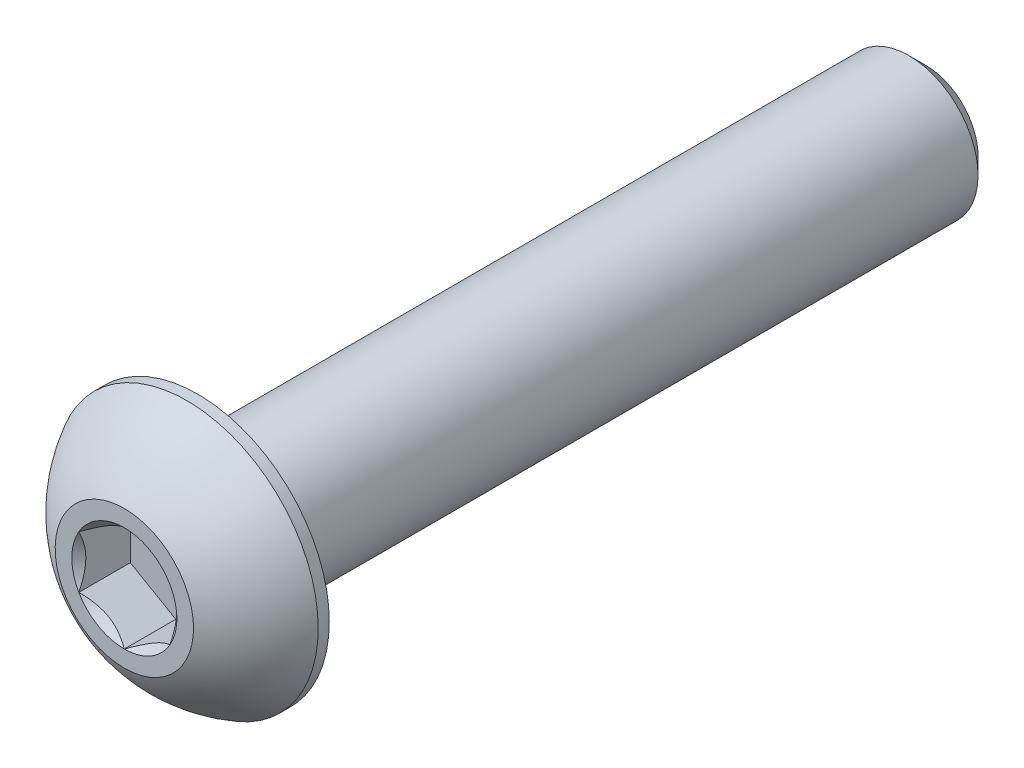
SolidWorks part; units mm, degrees
ref_plane "Front" through (0, 0, 0) normal (0, 0, 1) x (1, 0, 0)
ref_plane "Top" through (0, 0, 0) normal (0, 1, 0) x (1, 0, 0)
ref_plane "Right" through (0, 0, 0) normal (1, 0, 0) x (0, 0, -1)
sketch "Sketch1" plane through (0, 0, 0) normal (1, 0, 0) x (0, 0, -1)
  line L2 (2.5654, 2.413) -> (27.9654, 2.413)
  line L3 (27.9654, 2.413) -> (27.9654, 0)
  line L4 (27.9654, 0) -> (2.5654, 0)
  line L6 (2.1806, 4.5847) -> (2.5654, 4.5847) construction
  line L7 (27.9654, 2.413) -> (27.9654, -2.413) construction
  line L8 (0, 0) -> (2.5654, 0) construction
  line L9 (2.5654, 4.5847) -> (2.5654, -4.5847) construction
  line L11 (2.5654, 2.413) -> (2.5654, 0)
  line L13 (0, 1.5875) -> (0, -1.5875) construction
  line L14 (0, 1.5875) -> (0, 2.413) construction
  arc A3 (0, 2.413) -> (2.1806, 4.5847) centre (4.5749, 0) cw construction
  dimension "D1" = 0.3848
  dimension "Head Ht" = 2.5654
  dimension "Head Dia" = 9.1694
  dimension "Dia" = 4.826
  dimension "Lg" = 25.4
  dimension "Hex" = 3.175
revolve "Revolve1" add sketch "Sketch1" angle 360 mid plane about L4
sketch "Sketch3" plane through (0, 0, -27.9654) normal (0, 0, -1) x (-1, 0, 0)
  circle A0 centre (0, 0) radius 2.413
curve "Helix/Spiral1" [suppressed] pitch 0.7937 height 26.1937 turns 33
sketch "Sketch2" plane through (0, 0, 0) normal (1, 0, 0) x (0, 0, -1)
  line L0 (27.9654, 2.413) -> (28.6599, 2.413)
  line L1 (28.6599, 2.413) -> (28.3623, 1.8974)
  line L2 (28.3623, 1.8974) -> (28.2631, 1.8974)
  line L3 (28.2631, 1.8974) -> (27.9654, 2.413)
  line L4 (28.1142, 2.1552) -> (28.5111, 2.1552) construction
  dimension "D1" = 60
  dimension "D2" = 0.0992
  dimension "D3" = 0.3969
chamfer "Chamfer1" distance 0.5953 angle 45 1 edges at (0, 2.413, -27.9654)
sweep "Cut-Sweep1" [suppressed] cut profiles "Sketch2" path "Helix/Spiral1"
sketch "Sketch7" plane through (0, 0, 0) normal (1, 0, 0) x (0, 0, -1)
  line L6 (2.1806, 4.5847) -> (2.5654, 4.5847) construction
  line L8 (0, 0) -> (2.5654, 0) construction
  line L11 (2.5654, 4.5847) -> (2.5654, -4.5847) construction
  line L12 (2.1806, 4.5847) -> (2.5654, 4.5847)
  line L13 (0, 0) -> (2.5654, 0)
  line L14 (0, 1.5875) -> (0, -1.5875) construction
  line L15 (2.5654, 4.5847) -> (2.5654, 0)
  line L16 (0, 2.413) -> (0, 0)
  arc A2 (2.1806, 4.5847) -> (0, 2.413) centre (4.5749, 0) ccw construction
  arc A3 (2.1806, 4.5847) -> (0, 2.413) centre (4.5749, 0) ccw
revolve "Revolve2" add sketch "Sketch7" angle 360 mid plane about L13
sketch "Sketch5" plane through (0, 0, 0) normal (0, 0, 1) x (1, 0, 0)
  line L1 (1.5875, -0.9165) -> (1.5875, 0.9165)
  line L2 (1.5875, 0.9165) -> (0, 1.8331)
  line L3 (0, 1.8331) -> (-1.5875, 0.9165)
  line L4 (-1.5875, 0.9165) -> (-1.5875, -0.9165)
  line L5 (-1.5875, -0.9165) -> (0, -1.8331)
  line L6 (0, -1.8331) -> (1.5875, -0.9165)
  circle A0 centre (0, 0) radius 1.5875 construction
extrude "Cut-Extrude2" cut sketch "Sketch5" against normal blind 1.7958
sketch "Sketch6" plane through (0, 0, 0) normal (0, 0, 1) x (1, 0, 0)
  circle A0 centre (0, 0) radius 1.8331
extrude "Cut-Extrude3" cut sketch "Sketch6" against normal blind 1.7958 draft 45
sketch "Sketch9" [suppressed] plane through (0, 0, -2.5654) normal (0, 0, 1) x (1, 0, 0)
  circle A2 centre (0, 0) radius 2.413
extrude "Boss-Extrude2" [suppressed] add sketch "Sketch9" against normal offset from surface (9.525 mm away) 31.75
sketch "Sketch10" plane through (0, 0, 0) normal (1, 0, 0) x (0, 0, -1)
  line L0 (27.9654, 2.413) -> (27.9654, -2.413) construction
  point P0 (26.7748, -2.413)
  dimension "D1" = 1.1906
equation "\"D3@Helix/Spiral1\" = \"Lg@Sketch1\" + \"D4@Helix/Spiral1\""
equation "\"D2@Sketch2\" = \"D4@Helix/Spiral1\" * .125"
equation "\"D3@Sketch2\" = \"D4@Helix/Spiral1\" * .5"
equation "\"D1@Chamfer1\" = \"D4@Helix/Spiral1\" * .75"
equation "\"D1@Cut-Extrude2\" = \"Head Ht@Sketch1\" * .7"
equation "\"D1@Sketch1\" = \"Head Ht@Sketch1\" * .15"
equation "\"D1@Sketch10\" = \"D4@Helix/Spiral1\" * 1.5"
equation "\"D1@Cut-Extrude3\" = \"D1@Cut-Extrude2\""
